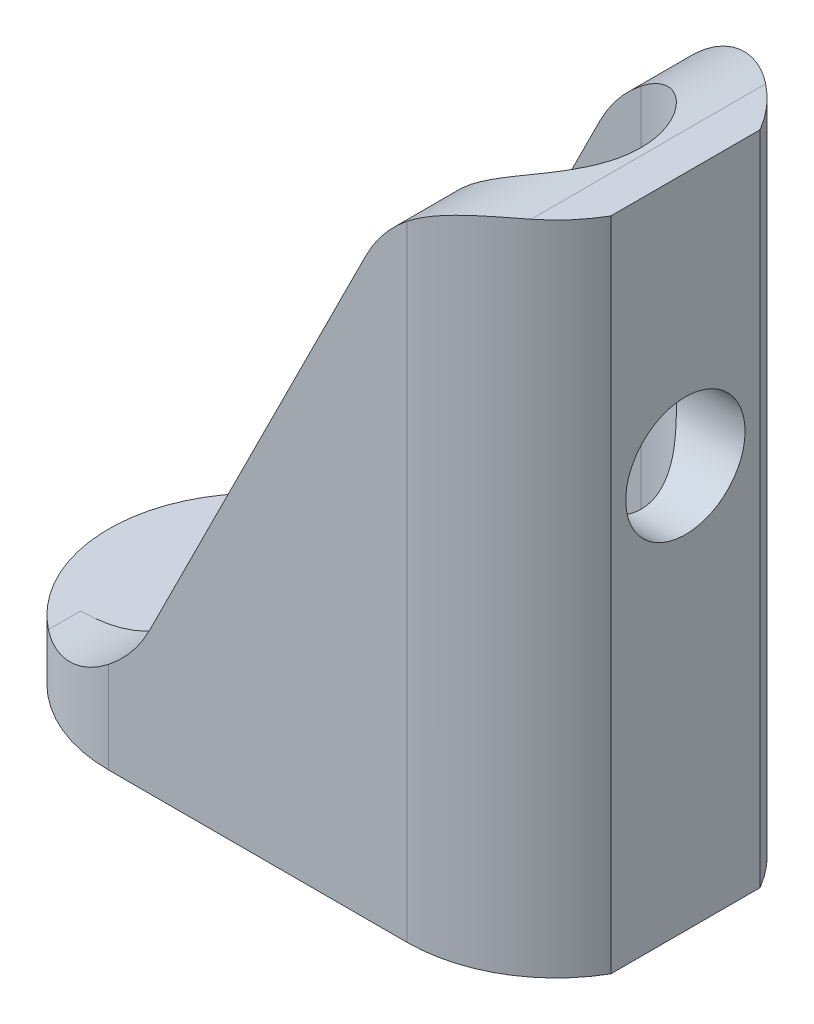
SolidWorks part; units mm, degrees
ref_plane "Front Plane" through (0, 0, 0) normal (0, 0, 1) x (1, 0, 0)
ref_plane "Top Plane" through (0, 0, 0) normal (0, 1, 0) x (1, 0, 0)
ref_plane "Right Plane" through (0, 0, 0) normal (1, 0, 0) x (0, 0, -1)
sketch "Sketch1" plane through (0, 0, 0) normal (0, 1, 0) x (1, 0, 0)
  line L0 (0, 0) -> (10, 0) construction
  line L1 (0, 2) -> (10, 2)
  line L2 (0, -2) -> (10, -2)
  line L3 (0, 5) -> (10, 5)
  line L4 (0, -5) -> (10, -5)
  arc A0 (0, 2) -> (0, -2) centre (0, 0) ccw
  arc A1 (10, -2) -> (10, 2) centre (10, 0) ccw
  arc A2 (10, -5) -> (10, 5) centre (10, 0) ccw
  arc A3 (0, 5) -> (0, -5) centre (0, 0) ccw
  point P3 (5, 0)
  dimension "D2" = 2
  dimension "D1" = 10
  dimension "D3" = 3
extrude "Boss-Extrude1" add sketch "Sketch1" along normal blind 2
sketch "Sketch2" plane through (0, 2, 0) normal (0, 1, 0) x (1, 0, 0)
  line L0 (12, 0) -> (0, 0) construction
  line L1 (0, -2.85) -> (10, -2.85)
  line L2 (0, -2.85) -> (0, -5)
  line L3 (0, -5) -> (10, -5)
  line L4 (10, -2.85) -> (10, -5)
  line L5 (10, 0) -> (10, -2.85) construction
  line L6 (12.85, 0) -> (15, 0) construction
  line L7 (10, 2.85) -> (10, 5)
  line L8 (0, 5) -> (10, 5)
  line L9 (0, 2.85) -> (0, 5)
  line L10 (0, 2.85) -> (10, 2.85)
  arc A0 (10, -2) -> (10, 2) centre (10, 0) ccw construction
  arc A1 (10, -2.85) -> (10, 2.85) centre (10, 0) ccw
  arc A2 (10, -5) -> (10, 5) centre (10, 0) ccw
  arc A4 (10, -5) -> (10, 5) centre (10, 0) ccw construction
  line M4 (0, -5) -> (10, -5)
  arc M5 (10, -5) -> (10, 5) centre (10, 0) ccw
  line M6 (10, 5) -> (0, 5)
  dimension "D1" = 2.85
extrude "Boss-Extrude2" add sketch "Sketch2" along normal blind 20 contours A1 L4 L7 M5 | L9 L10 L7 M6 | L4 L1 L2 M4 region at (5, 2, 3.925) region at (12.9618, 2, 0) region at (5, 2, -3.925)
sketch "Sketch3" plane through (0, 0, -5) normal (0, 0, -1) x (-1, 0, 0)
  line L0 (0, 2) -> (-10, 22)
  line L1 (-10, 22) -> (0, 22)
  line L2 (0, 22) -> (0, 2)
extrude "Cut-Extrude1" cut sketch "Sketch3" against normal through all
fillet "Fillet1" radius 5 4 edges at (0, 2, -3.925) (0, 2, 3.925) (10, 22, -3.925) (10, 22, 3.925)
sketch "Sketch4" plane through (0, 0, 0) normal (0, -1, 0) x (1, 0, 0)
  line L0 (14.3301, -2.5) -> (14.3301, 2.5)
  arc A1 (10, -5) -> (10, 5) centre (10, 0) ccw construction
  arc A2 (14.3301, 2.5) -> (14.3301, -2.5) centre (10, 0) cw
  arc M5 (10, -5) -> (10, 5) centre (10, 0) ccw
  dimension "D1" = 5
extrude "Cut-Extrude2" cut sketch "Sketch4" against normal through all contours L0 M5 region at (14.5997, 0, 0)
sketch "Sketch5" plane through (14.3301, 0, 0) normal (1, 0, 0) x (0, 0, -1)
  line L0 (0, 22) -> (0, 0) construction
  line L1 (2.5, 22) -> (-2.5, 22) construction
  circle A0 centre (0, 13.5) radius 2
  dimension "D2" = 4
  dimension "D1" = 8.5
extrude "Cut-Extrude3" cut sketch "Sketch5" against normal through all
